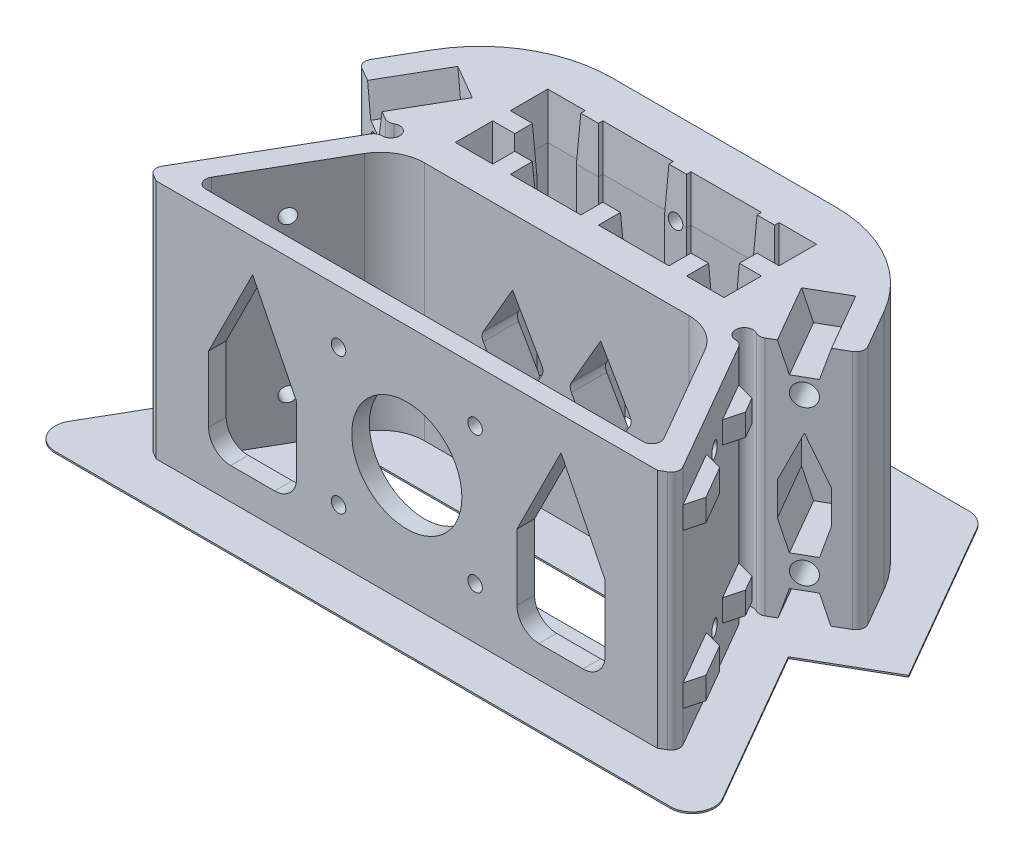
SolidWorks part; units mm, degrees
ref_plane "Front Plane" through (0, 0, 0) normal (0, 0, 1) x (1, 0, 0)
ref_plane "Top Plane" through (0, 0, 0) normal (0, 1, 0) x (1, 0, 0)
ref_plane "Right Plane" through (0, 0, 0) normal (1, 0, 0) x (0, 0, -1)
sketch "Sketch1" plane through (0, 0, 0) normal (0, 1, 0) x (1, 0, 0)
  line L0 (-30, -18) -> (30, -18)
  line L1 (-30, 10) -> (-22.5, 10)
  line L2 (-46.46, 5.4904) -> (-53.96, -7.5) construction
  line L3 (-30, -10) -> (-22.5, -10)
  line L4 (30, 10) -> (30, 2.5)
  line L5 (0, 0) -> (0, -75.5561) construction
  line L6 (38.6603, -23) -> (51.362, -45)
  line L7 (55.7735, -52.641) -> (58.3716, -51.141)
  line L8 (59.1036, -48.409) -> (41.8357, -18.5)
  line L9 (43.1036, -13.7679) -> (55.6921, -6.5)
  line L10 (56.4241, -3.7679) -> (51.362, 5)
  line L11 (25.3812, 20) -> (-25.3812, 20)
  line L12 (43.5677, -13.5) -> (36.0677, -0.5096) construction
  line L13 (36.0677, -0.5096) -> (46.46, 5.4904) construction
  line L14 (46.46, 5.4904) -> (53.96, -7.5) construction
  line L15 (-36.0677, -0.5096) -> (-46.46, 5.4904) construction
  line L16 (-43.5677, -13.5) -> (-36.0677, -0.5096) construction
  line L17 (-56.4241, -3.7679) -> (-51.362, 5)
  line L18 (-43.1036, -13.7679) -> (-55.6921, -6.5)
  line L19 (-59.1036, -48.409) -> (-41.8357, -18.5)
  line L20 (-55.7735, -52.641) -> (-58.3716, -51.141)
  line L21 (-38.6603, -23) -> (-51.362, -45)
  line L22 (-30, 10) -> (-30, 2.5)
  line L23 (30, 2.5) -> (25, 2.5)
  line L24 (25, 2.5) -> (25, -2.5)
  line L25 (25, -2.5) -> (30, -2.5)
  line L26 (30, -2.5) -> (30, -10)
  line L27 (22.5, -10) -> (22.5, -5)
  line L28 (22.5, -5) -> (17.5, -5)
  line L29 (17.5, -5) -> (17.5, -10)
  line L30 (22.5, -10) -> (30, -10)
  line L31 (17.5, 10) -> (17.5, 9)
  line L32 (17.5, 9) -> (22.5, 9)
  line L33 (22.5, 9) -> (22.5, 10)
  line L34 (22.5, 10) -> (30, 10)
  line L35 (2.5, -10) -> (2.5, -5)
  line L36 (2.5, -5) -> (-2.5, -5)
  line L37 (-2.5, -5) -> (-2.5, -10)
  line L38 (-2.5, 10) -> (-2.5, 9)
  line L39 (-2.5, 9) -> (2.5, 9)
  line L40 (2.5, 9) -> (2.5, 10)
  line L41 (-17.5, -10) -> (-17.5, -5)
  line L42 (-17.5, -5) -> (-22.5, -5)
  line L43 (-22.5, -5) -> (-22.5, -10)
  line L44 (-22.5, 10) -> (-22.5, 9)
  line L45 (-22.5, 9) -> (-17.5, 9)
  line L46 (-17.5, 9) -> (-17.5, 10)
  line L47 (-17.5, 10) -> (-2.5, 10)
  line L48 (-17.5, -10) -> (-2.5, -10)
  line L49 (2.5, -10) -> (17.5, -10)
  line L50 (2.5, 10) -> (17.5, 10)
  line L51 (-25, -2.5) -> (-30, -2.5)
  line L52 (-25, 2.5) -> (-25, -2.5)
  line L53 (-30, 2.5) -> (-25, 2.5)
  line L54 (-30, -2.5) -> (-30, -10)
  line L55 (-54.8261, -52) -> (54.8261, -52)
  line L56 (-49.6299, -48) -> (49.6299, -48)
  line L57 (-55.6921, -52.5) -> (-55.7735, -52.641)
  line L58 (55.6921, -52.5) -> (55.7735, -52.641)
  circle A0 centre (0, 0) radius 31.6228 construction
  arc A1 (30, -18) -> (38.6603, -23) centre (30, -28) cw
  arc A2 (51.362, 5) -> (25.3812, 20) centre (25.3812, -10) ccw
  arc A3 (41.1036, -13.7679) -> (40.1036, -17.5) centre (40.1036, -15.5) ccw
  arc A4 (58.3716, -51.141) -> (59.1036, -48.409) centre (57.3716, -49.409) ccw
  arc A5 (55.6921, -6.5) -> (56.4241, -3.7679) centre (54.6921, -4.7679) ccw
  arc A6 (40.1036, -17.5) -> (41.8357, -18.5) centre (40.1036, -19.5) cw
  arc A7 (41.1036, -13.7679) -> (43.1036, -13.7679) centre (42.1036, -12.0359) ccw
  arc A8 (-41.1036, -13.7679) -> (-43.1036, -13.7679) centre (-42.1036, -12.0359) cw
  arc A9 (-40.1036, -17.5) -> (-41.8357, -18.5) centre (-40.1036, -19.5) ccw
  arc A10 (-55.6921, -6.5) -> (-56.4241, -3.7679) centre (-54.6921, -4.7679) cw
  arc A11 (-58.3716, -51.141) -> (-59.1036, -48.409) centre (-57.3716, -49.409) cw
  arc A12 (-41.1036, -13.7679) -> (-40.1036, -17.5) centre (-40.1036, -15.5) cw
  arc A13 (-51.362, 5) -> (-25.3812, 20) centre (-25.3812, -10) cw
  arc A14 (-30, -18) -> (-38.6603, -23) centre (-30, -28) ccw
  arc A15 (55.6921, -52.5) -> (54.8261, -52) centre (54.8261, -53) ccw
  arc A16 (-54.8261, -52) -> (-55.6921, -52.5) centre (-54.8261, -53) ccw
  arc A17 (49.6299, -48) -> (51.362, -45) centre (49.6299, -46) ccw
  arc A18 (-49.6299, -48) -> (-51.362, -45) centre (-49.6299, -46) cw
  point P7 (-57.4241, -5.5)
  point P9 (0, -18)
  point P22 (35.7735, -18)
  point P27 (0, 10)
  point P30 (60.1036, -50.141)
  point P33 (57.4241, -5.5)
  point P61 (0, 20)
  point P65 (-60.1036, -50.141)
  point P66 (-35.7735, -18)
  point P104 (55.4034, -52)
  point P107 (-55.4034, -52)
  dimension "D12" = 10
  dimension "D14" = 30
  dimension "D16" = 2
  dimension "D17" = 2
  dimension "D28" = 1
  dimension "D29" = 2
  dimension "D2" = 30
  dimension "D3" = 5
  dimension "D4" = 8
  dimension "D5" = 40
  dimension "D6" = 20
  dimension "D7" = 30
  dimension "D8" = 10
  dimension "D9" = 4
  dimension "D10" = 12
  dimension "D11" = 15
  dimension "D13" = 20
  dimension "D15" = 34
  dimension "D18" = 5
  dimension "D19" = 2.5
  dimension "D20" = 5
  dimension "D21" = 5
  dimension "D22" = 5
  dimension "D23" = 7.5
  dimension "D24" = 1
  dimension "D26" = 20
  dimension "D27" = 4
  dimension "D25" = 3
extrude "Boss-Extrude1" add sketch "Sketch1" along normal blind 55
sketch "Sketch13" plane through (16.7376, 0, 28.9904) normal (0.5, 0, 0.866) x (0.866, 0, -0.5)
  line L0 (30.4449, 0) -> (44.9808, 0) construction
  line L1 (26.9808, 55) -> (26.9808, 0) construction
  line L2 (30.4449, 55) -> (44.9808, 55) construction
  circle A0 centre (36.9808, 10) radius 5
  circle A1 centre (36.9808, 45) radius 5
  dimension "D2" = 10
  dimension "D1" = 10
  dimension "D3" = 10
  dimension "D5" = 10
  dimension "D4" = 2
extrude "Cut-Extrude7" cut sketch "Sketch13" against normal through all
sketch "Sketch14" plane through (16.7376, 0, 28.9904) normal (0.5, 0, 0.866) x (0.866, 0, -0.5)
  circle A0 centre (36.9808, 45) radius 5
  circle A1 centre (36.9808, 10) radius 5
  circle A2 centre (36.9808, 45) radius 5 construction
  circle A3 centre (36.9808, 10) radius 5 construction
  circle A4 centre (36.9808, 45) radius 2.5
  circle A5 centre (36.9808, 10) radius 2.5
  dimension "D1" = 5
  dimension "D2" = 5
extrude "Boss-Extrude8" add sketch "Sketch14" against normal blind 16
sketch "Sketch15" plane through (16.7376, 0, 28.9904) normal (0.5, 0, 0.866) x (0.866, 0, -0.5)
  line L0 (32.4808, 55) -> (34.4808, 48.5)
  line L1 (24.9808, 27.5) -> (44.9808, 27.5) construction
  line L2 (30.4449, 55) -> (44.9808, 55) construction
  line L3 (34.4808, 48.5) -> (39.4808, 48.5)
  line L4 (39.4808, 48.5) -> (41.4808, 55)
  line L5 (41.4808, 55) -> (32.4808, 55)
  line L6 (36.9808, 48.5) -> (36.9808, 55) construction
  line L7 (26.9808, 55) -> (26.9808, 0) construction
  line L8 (24.9808, 55) -> (24.9808, 0) construction
  line L9 (44.9808, 55) -> (44.9808, 0) construction
  line L10 (39.4808, 6.5) -> (41.4808, 0)
  line L11 (34.4808, 6.5) -> (39.4808, 6.5)
  line L12 (32.4808, 0) -> (34.4808, 6.5)
  line L13 (41.4808, 0) -> (32.4808, 0)
  line L14 (28.7128, 10) -> (36.9808, 10) construction
  line L15 (28.7128, 55) -> (28.7128, 0) construction
  line L16 (41.4808, 20) -> (41.4808, 27.5)
  line L17 (32.4808, 20) -> (34.4808, 13.5)
  line L18 (34.4808, 13.5) -> (39.4808, 13.5)
  line L19 (39.4808, 13.5) -> (41.4808, 20)
  line L20 (41.4808, 27.5) -> (36.9808, 37.5)
  line L21 (36.9808, 37.5) -> (32.4808, 27.5)
  line L22 (32.4808, 27.5) -> (32.4808, 20)
  dimension "D1" = 9
  dimension "D2" = 5
  dimension "D3" = 10
  dimension "D4" = 6.5
  dimension "D5" = 10
extrude "Cut-Extrude8" cut sketch "Sketch15" against normal blind 15
sketch "Sketch16" plane through (23.366, 0, -13.4904) normal (0.866, 0, -0.5) x (-0.5, 0, -0.866)
  line L0 (-71.4752, 55) -> (-71.4752, 0) construction
  line L1 (-71.4752, 7.5) -> (-56.9393, 7.5)
  line L2 (-71.4752, 7.5) -> (-71.4752, 12.5)
  line L3 (-71.4752, 12.5) -> (-56.9393, 12.5)
  line L4 (-36.9393, 7.5) -> (-36.9393, 12.5)
  line L5 (-36.9393, 55) -> (-36.9393, 0) construction
  line L6 (-71.4752, 0) -> (-36.9393, 0) construction
  line L7 (-71.4752, 47.5) -> (-56.9393, 47.5)
  line L8 (-71.4752, 47.5) -> (-71.4752, 42.5)
  line L9 (-71.4752, 42.5) -> (-56.9393, 42.5)
  line L10 (-36.9393, 47.5) -> (-36.9393, 42.5)
  line L11 (-71.4752, 55) -> (-36.9393, 55) construction
  line L12 (-56.9393, 47.5) -> (-56.9393, 42.5)
  line L13 (-46.9393, 7.5) -> (-46.9393, 12.5)
  line L14 (-46.9393, 47.5) -> (-36.9393, 47.5)
  line L15 (-46.9393, 42.5) -> (-36.9393, 42.5)
  line L16 (-46.9393, 12.5) -> (-36.9393, 12.5)
  line L17 (-46.9393, 7.5) -> (-36.9393, 7.5)
  line L18 (-46.9393, 42.5) -> (-46.9393, 47.5)
  line L19 (-56.9393, 12.5) -> (-56.9393, 7.5)
  dimension "D1" = 5
  dimension "D2" = 5
  dimension "D3" = 7.5
  dimension "D4" = 7.5
  dimension "D5" = 10
  dimension "D6" = 10
extrude "Boss-Extrude9" add sketch "Sketch16" along normal blind 3
chamfer "Chamfer2" distance 3 angle 45 8 edges at (44.4338, 45, 17) (44.4338, 10, 17) (49.4338, 10, 25.6603) (49.4338, 45, 25.6603) (54.4338, 45, 34.3205) (54.4338, 10, 34.3205) (61.7017, 10, 46.909) (61.7017, 45, 46.909)
sketch "Sketch17" plane through (23.366, 0, -13.4904) normal (0.866, 0, -0.5) x (-0.5, 0, -0.866)
  line L0 (-56.9393, 45) -> (-46.9393, 45) construction
  line L1 (-56.9393, 42.5) -> (-56.9393, 47.5) construction
  line L2 (-46.9393, 47.5) -> (-46.9393, 42.5) construction
  line L3 (-51.9393, 45) -> (-51.9393, 10) construction
  line L4 (-56.9393, 10) -> (-46.9393, 10) construction
  line L5 (-56.9393, 7.5) -> (-56.9393, 12.5) construction
  line L6 (-46.9393, 12.5) -> (-46.9393, 7.5) construction
  circle A0 centre (-51.9393, 10) radius 1.65
  circle A1 centre (-51.9393, 45) radius 1.65
  dimension "D1" = 3.3
  dimension "D2" = 2
extrude "Cut-Extrude9" cut sketch "Sketch17" against normal up to next
mirror "Mirror7" about plane through (0, 0, 0) normal (1, 0, 0) of "Cut-Extrude9", "Chamfer2", "Boss-Extrude9", "Cut-Extrude8", "Boss-Extrude8", "Cut-Extrude7"
sketch "Sketch18" plane through (0, 0, -20) normal (0, 0, -1) x (-1, 0, 0)
  line L0 (-25.3812, 27.5) -> (25.3812, 27.5) construction
  line L1 (-25.3812, 45) -> (-25.3812, 10) construction
  line L2 (25.3812, 45) -> (25.3812, 10) construction
  line L3 (0, 0) -> (0, 55) construction
  line L4 (-25.3812, 55) -> (25.3812, 55) construction
  line L5 (-25.3812, 0) -> (25.3812, 0) construction
  circle A0 centre (0, 45) radius 1.65
  circle A1 centre (0, 10) radius 1.65
  circle A2 centre (-20, 27.5) radius 1.65
  circle A3 centre (20, 27.5) radius 1.65
  dimension "D1" = 3.3
  dimension "D2" = 3.3
  dimension "D3" = 3.3
  dimension "D4" = 3.3
  dimension "D6" = 10
  dimension "D8" = 20
  dimension "D5" = 10
  dimension "D7" = 20
extrude "Cut-Extrude10" cut sketch "Sketch18" against normal up to next
sketch "Sketch19" plane through (0, 0, -20) normal (0, 0, -1) x (-1, 0, 0)
  circle A0 centre (0, 45) radius 6
  circle A1 centre (20, 27.5) radius 6
  circle A2 centre (0, 10) radius 6
  circle A3 centre (-20, 27.5) radius 6
  dimension "D1" = 12
  dimension "D2" = 12
  dimension "D3" = 12
  dimension "D4" = 12
extrude "Cut-Extrude11" cut sketch "Sketch19" against normal offset from surface (4 mm away) 7 up to face at (1.65, 10, -9)
sketch "Sketch20" plane through (0, 0, 18) normal (0, 0, 1) x (1, 0, 0)
  line L0 (-10, 40) -> (-16.6395, 28.5)
  line L1 (-16.6395, 26.5) -> (-11.7321, 18)
  line L2 (-8.2679, 18) -> (-3.3605, 26.5)
  line L3 (-3.3605, 28.5) -> (-10, 40)
  line L4 (-17.2169, 27.5) -> (-30, 27.5) construction
  line L5 (-30, 55) -> (-30, 0) construction
  line L6 (0, 0) -> (0, 55) construction
  line L7 (-30, 55) -> (30, 55) construction
  line L8 (3.3605, 28.5) -> (10, 40)
  line L9 (8.2679, 18) -> (3.3605, 26.5)
  line L10 (16.6395, 26.5) -> (11.7321, 18)
  line L11 (10, 40) -> (16.6395, 28.5)
  arc A0 (-3.3605, 26.5) -> (-3.3605, 28.5) centre (-5.0925, 27.5) ccw
  arc A1 (-16.6395, 28.5) -> (-16.6395, 26.5) centre (-14.9075, 27.5) ccw
  arc A2 (-11.7321, 18) -> (-8.2679, 18) centre (-10, 19) ccw
  arc A3 (11.7321, 18) -> (8.2679, 18) centre (10, 19) cw
  arc A4 (16.6395, 28.5) -> (16.6395, 26.5) centre (14.9075, 27.5) cw
  arc A5 (3.3605, 26.5) -> (3.3605, 28.5) centre (5.0925, 27.5) cw
  point P10 (-2.7831, 27.5)
  point P16 (-10, 15)
  point P31 (10, 15)
  point P32 (2.7831, 27.5)
  dimension "D6" = 2
  dimension "D1" = 60
  dimension "D2" = 60
  dimension "D3" = 120
  dimension "D4" = 25
  dimension "D5" = 10
extrude "Cut-Extrude12" cut sketch "Sketch20" against normal up to next
sketch "Sketch21" plane through (0, 0, 0) normal (0, 1, 0) x (1, 0, 0)
  line L0 (-30, -18) -> (30, -18) construction
  circle A0 centre (0, -18) radius 80
  dimension "D1" = 160
sketch "Sketch22" plane through (0, 55, 0) normal (0, 1, 0) x (1, 0, 0)
  line L0 (-54.8261, -52) -> (54.8261, -52) construction
  line L1 (-56.8838, -52) -> (56.8838, -52)
  line L2 (-56.8838, -52) -> (-56.8838, -52.641)
  line L3 (-56.8838, -52.641) -> (56.8838, -52.641)
  line L4 (56.8838, -52) -> (56.8838, -52.641)
  line L5 (-58.3716, -51.141) -> (-55.7735, -52.641) construction
  line L6 (55.7735, -52.641) -> (58.3716, -51.141) construction
extrude "Cut-Extrude13" cut sketch "Sketch22" against normal through all
sketch "Sketch23" plane through (0, 0, 52) normal (0, 0, 1) x (1, 0, 0)
  line L0 (0, 0) -> (0, 27.5) construction
  line L1 (0, 27.5) -> (56.8838, 27.5) construction
  line L2 (56.8838, 0) -> (56.8838, 55) construction
  line L3 (35, 7.5) -> (35, 47.5) construction
  line L4 (35, 47.5) -> (45, 27.5)
  line L5 (45, 27.5) -> (45, 7.5)
  line L6 (45, 7.5) -> (25, 7.5)
  line L7 (25, 27.5) -> (35, 47.5)
  line L8 (25, 7.5) -> (25, 27.5)
  line L9 (-45, 27.5) -> (-45, 7.5)
  line L10 (-45, 7.5) -> (-25, 7.5)
  line L11 (-25, 7.5) -> (-25, 27.5)
  line L12 (-35, 47.5) -> (-45, 27.5)
  line L13 (-25, 27.5) -> (-35, 47.5)
  circle A0 centre (0, 27.5) radius 12.5
  circle A1 centre (-15.5, 12) radius 1.65
  circle A2 centre (15.5, 12) radius 1.65
  circle A3 centre (15.5, 43) radius 1.65
  circle A4 centre (-15.5, 43) radius 1.65
  dimension "D1" = 25
  dimension "D2" = 3.3
  dimension "D4" = 15.5
  dimension "D8" = 31
  dimension "D3" = 15.5
  dimension "D7" = 31
  dimension "D9" = 20
  dimension "D10" = 20
  dimension "D11" = 40
  dimension "D12" = 35
  dimension "D5" = 2
  dimension "D6" = 2
extrude "Cut-Extrude14" cut sketch "Sketch23" against normal up to next
fillet "Fillet1" radius 5 4 edges at (45, 7.5, 50) (25, 7.5, 50) (-25, 7.5, 50) (-45, 7.5, 50)
chamfer "Chamfer3" distance 0.5 distance2 10 36 edges at (-30, 55, -6.25) (-27.5, 55, -2.5) (-25, 55, 0) (-27.5, 55, 2.5) (-30, 55, 6.25) (-26.25, 55, 10) (-22.5, 55, 7.5) (-20, 55, 5) (-17.5, 55, 7.5) (-10, 55, 10) (-2.5, 55, 7.5) (0, 55, 5) (2.5, 55, 7.5) (10, 55, 10) (17.5, 55, 7.5) (20, 55, 5) (22.5, 55, 7.5) (26.25, 55, 10) (30, 55, 6.25) (27.5, 55, 2.5) (25, 55, 0) (27.5, 55, -2.5) (30, 55, -6.25) (26.25, 55, -10) (22.5, 55, -9.5) (20, 55, -9) (17.5, 55, -9.5) (10, 55, -10) (2.5, 55, -9.5) (0, 55, -9) (-2.5, 55, -9.5) (-10, 55, -10) (-17.5, 55, -9.5) (-20, 55, -9) (-22.5, 55, -9.5) (-26.25, 55, -10) first distance on face at (0, 55, 14.172)
sketch "Sketch25" plane through (0, 0, 0) normal (0, 1, 0) x (1, 0, 0)
  line L0 (-30, 10) -> (-30, 2.5) construction
  line L1 (-22.5, 10) -> (-30, 10) construction
  line L2 (-22.5, 9) -> (-22.5, 10) construction
  line L3 (-17.5, 9) -> (-22.5, 9) construction
  line L4 (-17.5, 10) -> (-17.5, 9) construction
  line L5 (-2.5, 10) -> (-17.5, 10) construction
  line L6 (-2.5, 9) -> (-2.5, 10) construction
  line L7 (-1.65, 9) -> (-2.5, 9) construction
  line L8 (-1.65, 9) -> (1.65, 9) construction
  line L9 (2.5, 9) -> (1.65, 9) construction
  line L10 (2.5, 10) -> (2.5, 9) construction
  line L11 (17.5, 10) -> (2.5, 10) construction
  line L12 (17.5, 9) -> (17.5, 10) construction
  line L13 (22.5, 9) -> (17.5, 9) construction
  line L14 (22.5, 10) -> (22.5, 9) construction
  line L15 (30, 10) -> (22.5, 10) construction
  line L16 (30, 2.5) -> (30, 10) construction
  line L17 (25, 2.5) -> (30, 2.5) construction
  line L18 (25, -2.5) -> (25, 2.5) construction
  line L19 (30, -2.5) -> (25, -2.5) construction
  line L20 (30, -10) -> (30, -2.5) construction
  line L21 (22.5, -10) -> (30, -10) construction
  line L22 (22.5, -5) -> (22.5, -10) construction
  line L23 (17.5, -5) -> (22.5, -5) construction
  line L24 (17.5, -10) -> (17.5, -5) construction
  line L25 (2.5, -10) -> (17.5, -10) construction
  line L26 (2.5, -5) -> (2.5, -10) construction
  line L27 (-2.5, -5) -> (2.5, -5) construction
  line L28 (-2.5, -10) -> (-2.5, -5) construction
  line L29 (-17.5, -10) -> (-2.5, -10) construction
  line L30 (-17.5, -5) -> (-17.5, -10) construction
  line L31 (-22.5, -5) -> (-17.5, -5) construction
  line L32 (-22.5, -10) -> (-22.5, -5) construction
  line L33 (-30, -10) -> (-22.5, -10) construction
  line L34 (-30, -2.5) -> (-30, -10) construction
  line L35 (-25, -2.5) -> (-30, -2.5) construction
  line L36 (-25, 2.5) -> (-25, -2.5) construction
  line L37 (-30, 2.5) -> (-25, 2.5) construction
  line L38 (-30, 10) -> (-30, 2.5)
  line L39 (-22.5, 10) -> (-30, 10)
  line L40 (-22.5, 9) -> (-22.5, 10)
  line L41 (-17.5, 9) -> (-22.5, 9)
  line L42 (-17.5, 10) -> (-17.5, 9)
  line L43 (-2.5, 10) -> (-17.5, 10)
  line L44 (-2.5, 9) -> (-2.5, 10)
  line L45 (-1.65, 9) -> (-2.5, 9)
  line L46 (-1.65, 9) -> (1.65, 9)
  line L47 (2.5, 9) -> (1.65, 9)
  line L48 (2.5, 10) -> (2.5, 9)
  line L49 (17.5, 10) -> (2.5, 10)
  line L50 (17.5, 9) -> (17.5, 10)
  line L51 (22.5, 9) -> (17.5, 9)
  line L52 (22.5, 10) -> (22.5, 9)
  line L53 (30, 10) -> (22.5, 10)
  line L54 (30, 2.5) -> (30, 10)
  line L55 (25, 2.5) -> (30, 2.5)
  line L56 (25, -2.5) -> (25, 2.5)
  line L57 (30, -2.5) -> (25, -2.5)
  line L58 (30, -10) -> (30, -2.5)
  line L59 (22.5, -10) -> (30, -10)
  line L60 (22.5, -5) -> (22.5, -10)
  line L61 (17.5, -5) -> (22.5, -5)
  line L62 (17.5, -10) -> (17.5, -5)
  line L63 (2.5, -10) -> (17.5, -10)
  line L64 (2.5, -5) -> (2.5, -10)
  line L65 (-2.5, -5) -> (2.5, -5)
  line L66 (-2.5, -10) -> (-2.5, -5)
  line L67 (-17.5, -10) -> (-2.5, -10)
  line L68 (-17.5, -5) -> (-17.5, -10)
  line L69 (-22.5, -5) -> (-17.5, -5)
  line L70 (-22.5, -10) -> (-22.5, -5)
  line L71 (-30, -10) -> (-22.5, -10)
  line L72 (-30, -2.5) -> (-30, -10)
  line L73 (-25, -2.5) -> (-30, -2.5)
  line L74 (-25, 2.5) -> (-25, -2.5)
  line L75 (-30, 2.5) -> (-25, 2.5)
  line L76 (-69.8372, -62) -> (69.8372, -62)
  line L77 (74.1673, -54.5) -> (53.7639, -19.1603)
  line L78 (53.7639, -19.1603) -> (71.0844, -9.1603)
  line L79 (71.0844, -9.1603) -> (49.9186, 27.5)
  line L80 (45.5885, 30) -> (-45.5885, 30)
  line L81 (-49.9186, 27.5) -> (-71.0844, -9.1603)
  line L82 (-71.0844, -9.1603) -> (-53.7639, -19.1603)
  line L83 (-53.7639, -19.1603) -> (-74.1673, -54.5)
  line L84 (25.3812, 20) -> (-25.3812, 20) construction
  line L86 (56.4241, -3.7679) -> (51.362, 5) construction
  line L87 (46.5988, -11.75) -> (50.9289, -9.25) construction
  line L88 (59.1036, -48.409) -> (41.8357, -18.5) construction
  line L89 (-56.8838, -52) -> (56.8838, -52) construction
  line L90 (-51.362, 5) -> (-56.4241, -3.7679) construction
  line L91 (-46.5988, -11.75) -> (-50.9289, -9.25) construction
  line L93 (-41.8357, -18.5) -> (-59.1036, -48.409) construction
  line L94 (-35.7735, -38) -> (35.7735, -38)
  line L95 (35.7735, -38) -> (30, -28)
  line L96 (30, -28) -> (-30, -28)
  line L97 (-30, -28) -> (-35.7735, -38)
  line L98 (-38.6603, -23) -> (-51.362, -45) construction
  line L99 (-49.6299, -48) -> (49.6299, -48) construction
  line L100 (10, -18) -> (3.3605, -18) construction
  line L101 (51.362, -45) -> (38.6603, -23) construction
  arc A0 (69.8372, -62) -> (74.1673, -54.5) centre (69.8372, -57) ccw
  arc A1 (49.9186, 27.5) -> (45.5885, 30) centre (45.5885, 25) ccw
  arc A2 (-45.5885, 30) -> (-49.9186, 27.5) centre (-45.5885, 25) ccw
  arc A3 (-69.8372, -62) -> (-74.1673, -54.5) centre (-69.8372, -57) cw
  point P78 (6.6802, -18)
  dimension "D9" = 5
  dimension "D1" = 10
  dimension "D2" = 10
  dimension "D3" = 10
  dimension "D4" = 10
  dimension "D5" = 10
  dimension "D6" = 10
  dimension "D7" = 10
  dimension "D8" = 10
  dimension "D10" = 10
  dimension "D11" = 10
  dimension "D12" = 10
  dimension "D13" = 10
extrude "Boss-Extrude10" add sketch "Sketch25" along normal blind 0.35
